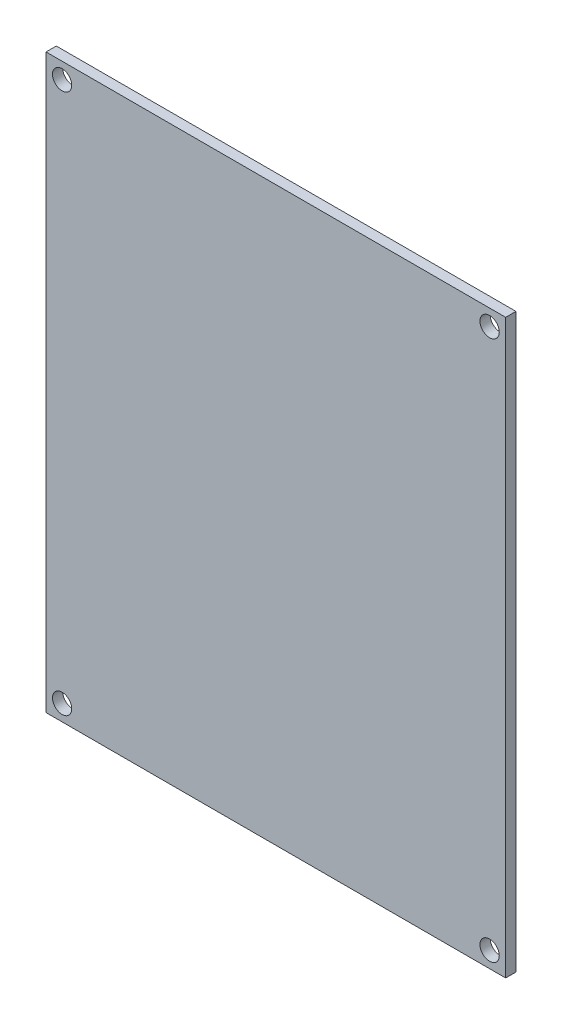
SolidWorks part; units mm, degrees
material "Delrin 2700 NC010, Low Viscosity Acetal Copolymer (SS)"
ref_plane "Alzado" through (0, 0, 0) normal (0, 0, 1) x (1, 0, 0)
ref_plane "Planta" through (0, 0, 0) normal (0, 1, 0) x (1, 0, 0)
ref_plane "Vista lateral" through (0, 0, 0) normal (1, 0, 0) x (0, 0, -1)
sketch "Sketch1" plane through (0, 0, 0) normal (0, 0, 1) x (1, 0, 0)
  line L0 (18.5, 42) -> (85, -42) construction
  line L2 (85, -42) -> (18.5, -42) construction
  line L3 (85, -42) -> (85, 42) construction
  line L4 (85, 42) -> (18.5, 42) construction
  line L5 (18.5, -42) -> (18.5, 42) construction
  line L6 (51.75, 42) -> (51.75, -42) construction
  line L7 (85, 0) -> (18.5, 0) construction
  line L9 (87.5, -44.5) -> (87.5, 44.5)
  line L10 (87.5, 44.5) -> (16, 44.5)
  line L11 (16, -44.5) -> (16, 44.5)
  line L12 (87.5, -44.5) -> (16, -44.5)
  circle A0 centre (18.5, -42) radius 1.5 construction
  circle A1 centre (85, -42) radius 1.5 construction
  circle A2 centre (85, 42) radius 1.5 construction
  circle A3 centre (18.5, 42) radius 1.5 construction
  circle A4 centre (18.5, -42) radius 1.5
  circle A5 centre (85, -42) radius 1.5
  circle A6 centre (85, 42) radius 1.5
  circle A7 centre (18.5, 42) radius 1.5
  point P12 (51.75, 0)
  dimension "D1" = 2.5
extrude "Boss-Extrude1" add sketch "Sketch1" along normal blind 1.6
